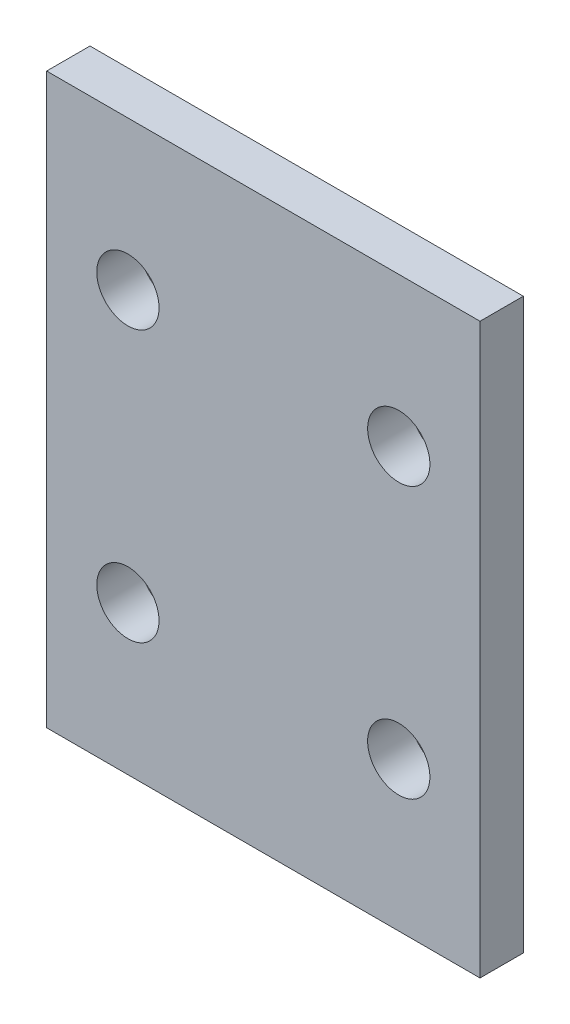
SolidWorks part; units mm, degrees
material "Простая углеродистая сталь"
ref_plane "Спереди" through (0, 0, 0) normal (0, 0, 1) x (1, 0, 0)
ref_plane "Сверху" through (0, 0, 0) normal (0, 1, 0) x (1, 0, 0)
ref_plane "Справа" through (0, 0, 0) normal (1, 0, 0) x (0, 0, -1)
sketch "Эскиз1" plane through (0, 0, 0) normal (0, 0, 1) x (1, 0, 0)
  line L0 (80, 0) -> (80, -210) construction
  line L1 (0, 0) -> (160, 0)
  line L2 (0, 0) -> (0, -210)
  line L3 (0, -210) -> (160, -210)
  line L4 (160, 0) -> (160, -210)
  line L5 (0, -105) -> (160, -105) construction
  circle A0 centre (30, -55) radius 11.5
  circle A1 centre (130, -55) radius 11.5
  circle A2 centre (130, -155) radius 11.5
  circle A3 centre (30, -155) radius 11.5
  dimension "D3" = 23
  dimension "D4" = 100
  dimension "D5" = 100
  dimension "D1" = 160
  dimension "D2" = 210
base flange "Базовая кромка1" sketch "Эскиз1" thickness 16 reverse thickness direction no parameters "D1"=3
sketch "Сгиб-Линии1" [suppressed] plane through (0, 0, 0) normal (0, 1, 0) x (1, 0, 0)
sketch "Граничная рамка1" [suppressed] plane through (0, 0, 0) normal (0, 1, 0) x (1, 0, 0)
sheet metal parameters "Листовой металл1" thickness 16 parameters "D1"=3
flat pattern "Развертка1" [suppressed]
sketch "Сгиб-Линии2" plane through (0, 0, 0) normal (0, 1, 0) x (1, 0, 0)
sketch3d "Граничная рамка2" [suppressed]
  line L0 (160, 0, 0) -> (160, -210, 0) construction
  line L1 (0, 0, 0) -> (0, -210, 0) construction
  line L2 (160, 0, 0) -> (0, 0, 0) construction
  line L3 (160, -210, 0) -> (0, -210, 0) construction
